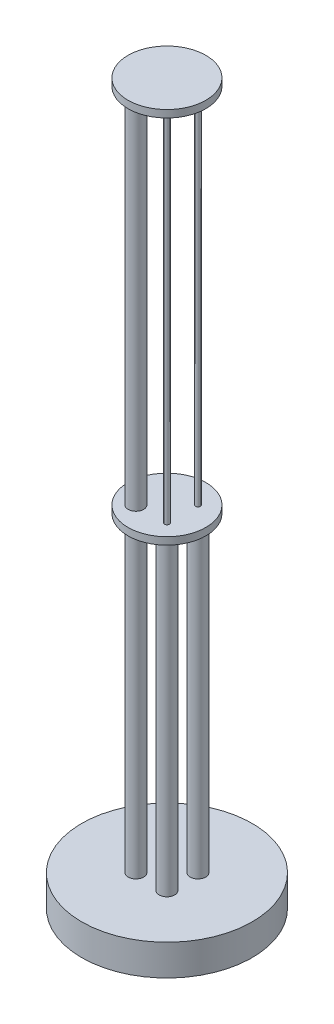
SolidWorks part; units mm, degrees
ref_plane "Front Plane" through (0, 0, 0) normal (0, 0, 1) x (1, 0, 0)
ref_plane "Top Plane" through (0, 0, 0) normal (0, 1, 0) x (1, 0, 0)
ref_plane "Right Plane" through (0, 0, 0) normal (1, 0, 0) x (0, 0, -1)
sketch "Sketch1" plane through (0, 0, 0) normal (0, 1, 0) x (1, 0, 0)
  circle A0 centre (0, 0) radius 34.925
  dimension "D1" = 69.85
extrude "Boss-Extrude1" add sketch "Sketch1" along normal blind 12.7
sketch "Sketch2" plane through (0, 12.7, 0) normal (0, 1, 0) x (1, 0, 0)
  line L0 (0, 0) -> (0, 21.305) construction
  line L1 (0, 0) -> (-21.023, 0) construction
  circle A0 centre (-6.35, 6.35) radius 3.175
  circle A1 centre (6.35, 6.35) radius 3.175
  circle A2 centre (6.35, -6.35) radius 3.175
  circle A3 centre (-6.35, -6.35) radius 3.175
  dimension "D1" = 6.35
  dimension "D2" = 12.7
  dimension "D3" = 12.7
extrude "Boss-Extrude2" add sketch "Sketch2" along normal blind 130.4
sketch "Sketch3" plane through (0, 143.1, 0) normal (0, 1, 0) x (1, 0, 0)
  circle A0 centre (-6.35, -6.35) radius 3.175
extrude "Boss-Extrude3" add sketch "Sketch3" along normal blind 151.5
sketch "Sketch4" plane through (0, 143.1, 0) normal (0, 1, 0) x (1, 0, 0)
  circle A0 centre (-6.35, 6.35) radius 1
  circle A1 centre (6.35, 6.35) radius 1
  circle A2 centre (6.35, -6.35) radius 1
  dimension "D1" = 2
extrude "Boss-Extrude4" add sketch "Sketch4" along normal up to surface (151.5 mm away) up to face at (-6.35, 294.6, 9.525)
sketch "Sketch5" plane through (0, 143.1, 0) normal (0, 1, 0) x (1, 0, 0)
  circle A0 centre (0, 0) radius 15.9414
extrude "Boss-Extrude5" add sketch "Sketch5" against normal blind 3
sketch "Sketch6" plane through (0, 294.6, 0) normal (0, 1, 0) x (1, 0, 0)
  circle A0 centre (0, 0) radius 15.9414
extrude "Boss-Extrude6" add sketch "Sketch6" against normal blind 3
